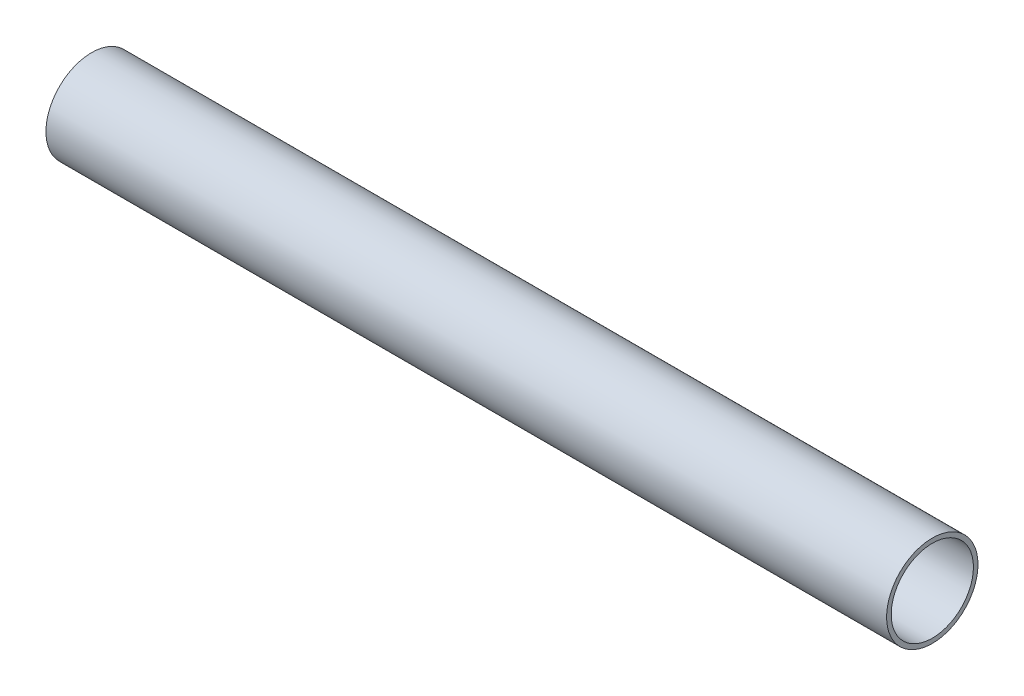
SolidWorks part; units mm, degrees
material "PC High Viscosity"
ref_plane "Front Plane" through (0, 0, 0) normal (0, 0, 1) x (1, 0, 0)
ref_plane "Top Plane" through (0, 0, 0) normal (0, 1, 0) x (1, 0, 0)
ref_plane "Right Plane" through (0, 0, 0) normal (1, 0, 0) x (0, 0, -1)
sketch "Sketch1" plane through (0, 0, 0) normal (1, 0, 0) x (0, 0, -1)
  circle A0 centre (0, 0) radius 15.875
  dimension "D1" = 31.75
extrude "Extrude-Thin1" add sketch "Sketch1" along normal mid plane 292.1 thin thin type one direction reverse wall 1.5875
